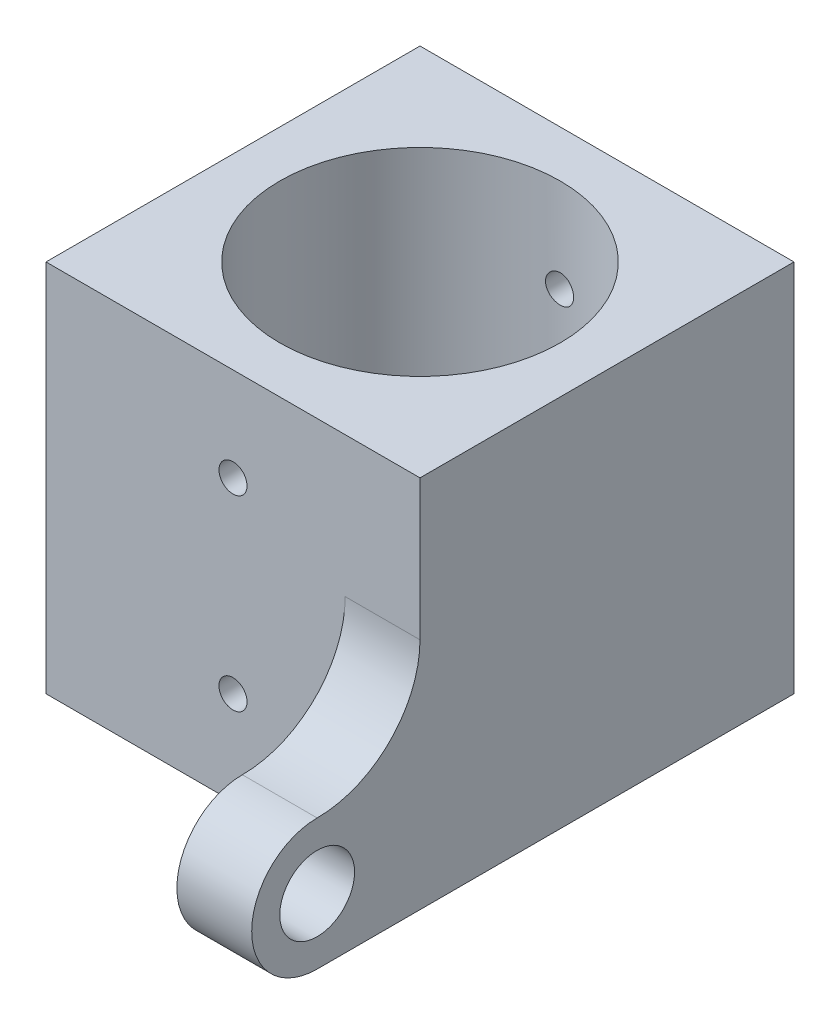
SolidWorks part; units mm, degrees
ref_plane "前基準面" through (0, 0, 0) normal (0, 0, 1) x (1, 0, 0)
ref_plane "上基準面" through (0, 0, 0) normal (0, 1, 0) x (1, 0, 0)
ref_plane "右基準面" through (0, 0, 0) normal (1, 0, 0) x (0, 0, -1)
sketch "草圖1" plane through (0, 0, 0) normal (0, 1, 0) x (1, 0, 0)
  line L1 (-20, 20) -> (20, 20)
  line L2 (-20, 20) -> (-20, -20)
  line L3 (-20, -20) -> (20, -20)
  line L4 (20, 20) -> (20, -20)
  line L5 (-20, 20) -> (20, -20) construction
  line L6 (-20, -20) -> (20, 20) construction
  circle A0 centre (0, 0) radius 15
  point P0 (0, 0)
  dimension "D3" = 30
  dimension "D1" = 40
  dimension "D2" = 40
extrude "填料-伸長1" add sketch "草圖1" along normal blind 40
sketch "草圖2" plane through (0, 0, 20) normal (0, 0, 1) x (1, 0, 0)
  line L0 (-20, 40) -> (20, 40) construction
  circle A0 centre (0, 10) radius 1.5
  circle A1 centre (0, 30) radius 1.5
  dimension "D1" = 3
  dimension "D2" = 10
  dimension "D3" = 10
extrude "除料-伸長1" cut sketch "草圖2" against normal through all
sketch "草圖3" plane through (20, 0, 0) normal (1, 0, 0) x (0, 0, -1)
  line L0 (-20, 0) -> (-31, 0)
  line L1 (-31, 14) -> (-20, 14)
  line L2 (-20, 40) -> (-20, 0) construction
  line L3 (-20, 14) -> (-20, 0)
  arc A0 (-31, 14) -> (-31, 0) centre (-31, 7) ccw
  circle A1 centre (-31, 7) radius 4
  dimension "D1" = 14
  dimension "D3" = 8
  dimension "D2" = 11
extrude "填料-伸長2" add sketch "草圖3" against normal blind 8
fillet "圓角1" radius 11 1 edges at (16, 14, 20)
